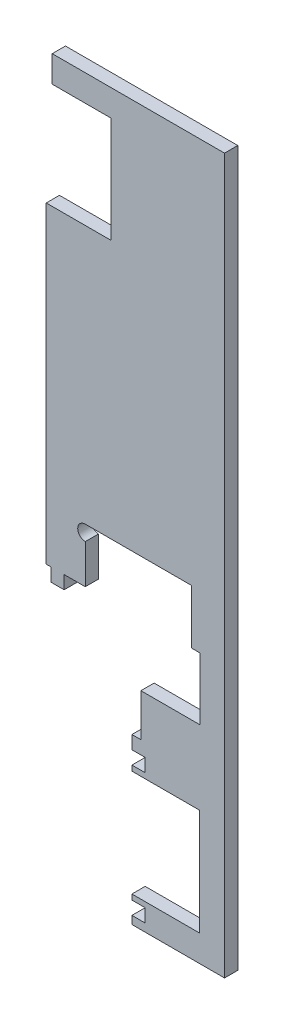
SolidWorks part; units mm, degrees
material "Balsa"
ref_plane "Plan de face" through (0, 0, 0) normal (0, 0, 1) x (1, 0, 0)
ref_plane "Plan de dessus" through (0, 0, 0) normal (0, 1, 0) x (1, 0, 0)
ref_plane "Plan de droite" through (0, 0, 0) normal (1, 0, 0) x (0, 0, -1)
sketch "Esquisse1" plane through (0, 0, 0) normal (0, 0, 1) x (1, 0, 0)
  line L0 (65.1211, 0) -> (30.1224, 0)
  line L2 (65.1211, 0) -> (65.1211, 270)
  line L3 (65.1211, 270) -> (0, 270)
  line L4 (0, 270) -> (0, 260)
  line L5 (0, 260) -> (22.181, 260)
  line L6 (-2.2595, 101.7504) -> (12.493, 101.7504)
  line L7 (12.493, 101.7504) -> (12.493, 122.247)
  line L8 (12.493, 122.247) -> (52.693, 122.247)
  line L9 (52.693, 122.247) -> (52.693, 101.7504)
  line L10 (52.693, 101.7504) -> (55.9116, 101.7504)
  line L11 (1.9558, 101.7504) -> (67.693, 101.7504) construction
  line L12 (55.9116, 101.7504) -> (55.9116, 78.2407)
  line L13 (55.9116, 78.2407) -> (33.5123, 78.2407)
  line L14 (33.5123, 78.2407) -> (33.5123, 62.2)
  line L15 (33.5123, 62.2) -> (30.1224, 62.2)
  line L16 (30.1224, 62.2) -> (30.1224, 57.2)
  line L17 (30.1224, 50.2) -> (55.6176, 50.2)
  line L18 (30.1224, 57.2) -> (35.1224, 57.2)
  line L19 (22.181, 260) -> (22.181, 220)
  line L20 (35.1224, 57.2) -> (35.1224, 52.2)
  line L21 (22.181, 220) -> (-2.2595, 220)
  line L22 (-2.2595, 220) -> (-2.2595, 101.7504)
  line L23 (35.1224, 52.2) -> (30.1224, 52.2)
  line L24 (30.1224, 52.2) -> (30.1224, 50.2)
  line L25 (30.1224, 0) -> (30.1224, 3)
  line L26 (30.1224, 3) -> (35.1224, 3)
  line L27 (35.1224, 3) -> (35.1224, 8)
  line L30 (35.1224, 8) -> (30.1224, 8)
  line L31 (30.1224, 8) -> (30.1224, 10)
  line L32 (30.1224, 10) -> (55.6176, 10)
  line L33 (55.6176, 10) -> (55.6176, 50.2)
  dimension "D1" = 270
  dimension "D2" = 65.1211
  dimension "D3" = 40.2
  dimension "D4" = 2
  dimension "D5" = 20.4965
  dimension "D6" = 40.2
  dimension "D7" = 40
  dimension "D8" = 10
  dimension "D9" = 12.4281
  dimension "D10" = 25.4952
  dimension "D11" = 5
  dimension "D12" = 5
  dimension "D13" = 5
  dimension "D14" = 2
  dimension "D15" = 5
  dimension "D16" = 5
  dimension "D17" = 25.4952
extrude "Boss.-Extru.1" add sketch "Esquisse1" against normal blind 5
sketch "Esquisse2" plane through (0, 0, 0) normal (0, 0, 1) x (1, 0, 0)
  line L2 (12.493, 122.247) -> (52.693, 122.247) construction
  line L3 (12.493, 101.7504) -> (12.493, 122.247) construction
  circle A0 centre (12.493, 119.3895) radius 2.8575
  dimension "D1" = 2.8575
extrude "Enlèv. mat.-Extru.1" cut sketch "Esquisse2" against normal blind 5
sketch "Esquisse3" plane through (0, 0, 0) normal (0, 0, 1) x (1, 0, 0)
  line L1 (4.493, 101.7504) -> (-0.507, 101.7504)
  line L2 (4.493, 101.7504) -> (4.493, 96.7504)
  line L3 (4.493, 96.7504) -> (-0.507, 96.7504)
  line L4 (-0.507, 101.7504) -> (-0.507, 96.7504)
  line L6 (-2.2595, 101.7504) -> (12.493, 101.7504) construction
  line L7 (12.493, 101.7504) -> (12.493, 116.532) construction
  dimension "D1" = 8
  dimension "D2" = 5
  dimension "D3" = 5
extrude "Boss.-Extru.2" add sketch "Esquisse3" against normal blind 5
